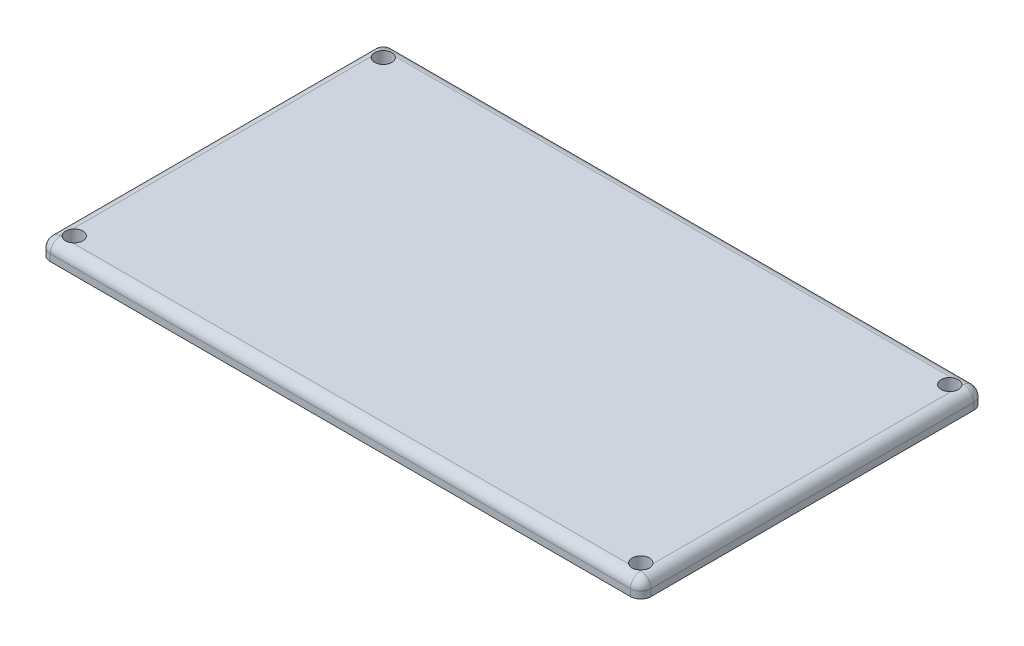
SolidWorks part; units mm, degrees
ref_plane "Front Plane" through (0, 0, 0) normal (0, 0, 1) x (1, 0, 0)
ref_plane "Top Plane" through (0, 0, 0) normal (0, 1, 0) x (1, 0, 0)
ref_plane "Right Plane" through (0, 0, 0) normal (1, 0, 0) x (0, 0, -1)
sketch "Sketch1" plane through (0, 0, 0) normal (0, 1, 0) x (1, 0, 0)
  line L0 (0, 0) -> (-65233.1732, 0) construction
  line L1 (0, 0) -> (0, -65233.1732) construction
  line L3 (-87.5, 50) -> (87.5, 50)
  line L4 (-87.5, 50) -> (-87.5, -50)
  line L5 (-87.5, -50) -> (87.5, -50)
  line L6 (87.5, 50) -> (87.5, -50)
  line L7 (-87.5, 50) -> (87.5, -50) construction
  line L8 (-87.5, -50) -> (87.5, 50) construction
  point P5 (0, 0)
  dimension "D1" = 175
  dimension "D2" = 100
extrude "Boss-Extrude1" add sketch "Sketch1" along normal blind 5
sketch "Sketch2" plane through (0, 5, 0) normal (0, 1, 0) x (1, 0, 0)
  line L0 (0, 0) -> (-50000, 0) construction
  line L1 (0, 0) -> (0, -50000) construction
  line L2 (77.5, -40) -> (77.5, 40) construction
  line L3 (77.5, 40) -> (-77.5, 40) construction
  line L4 (-77.5, 40) -> (-77.5, -40) construction
  line L5 (-77.5, -40) -> (77.5, -40) construction
  line L6 (87.5, -50) -> (87.5, 50)
  line L7 (87.5, 50) -> (-87.5, 50)
  line L8 (-87.5, 50) -> (-87.5, -50)
  line L9 (-87.5, -50) -> (87.5, -50)
  line L10 (87.5, -50) -> (87.5, 50) construction
  line L11 (87.5, 50) -> (-87.5, 50) construction
  line L12 (-87.5, 50) -> (-87.5, -50) construction
  line L13 (-87.5, -50) -> (87.5, -50) construction
  line L14 (-77.5, 40) -> (-87.5, 50) construction
  circle A0 centre (-82.5, 45) radius 2.5
  circle A1 centre (82.5, 45) radius 2.5
  circle A2 centre (82.5, -45) radius 2.5
  circle A3 centre (-82.5, -45) radius 2.5
  dimension "D3" = 5
  dimension "D1" = 0
  dimension "D2" = 10
extrude "Cut-Extrude1" cut sketch "Sketch2" against normal through all
fillet "Fillet1" radius 3 8 edges at (-87.5, 5, 0) (0, 5, 50) (87.5, 5, 0) (0, 5, -50) (87.5, 2.5, 50) (87.5, 2.5, -50) (-87.5, 2.5, 50) (-87.5, 2.5, -50)
